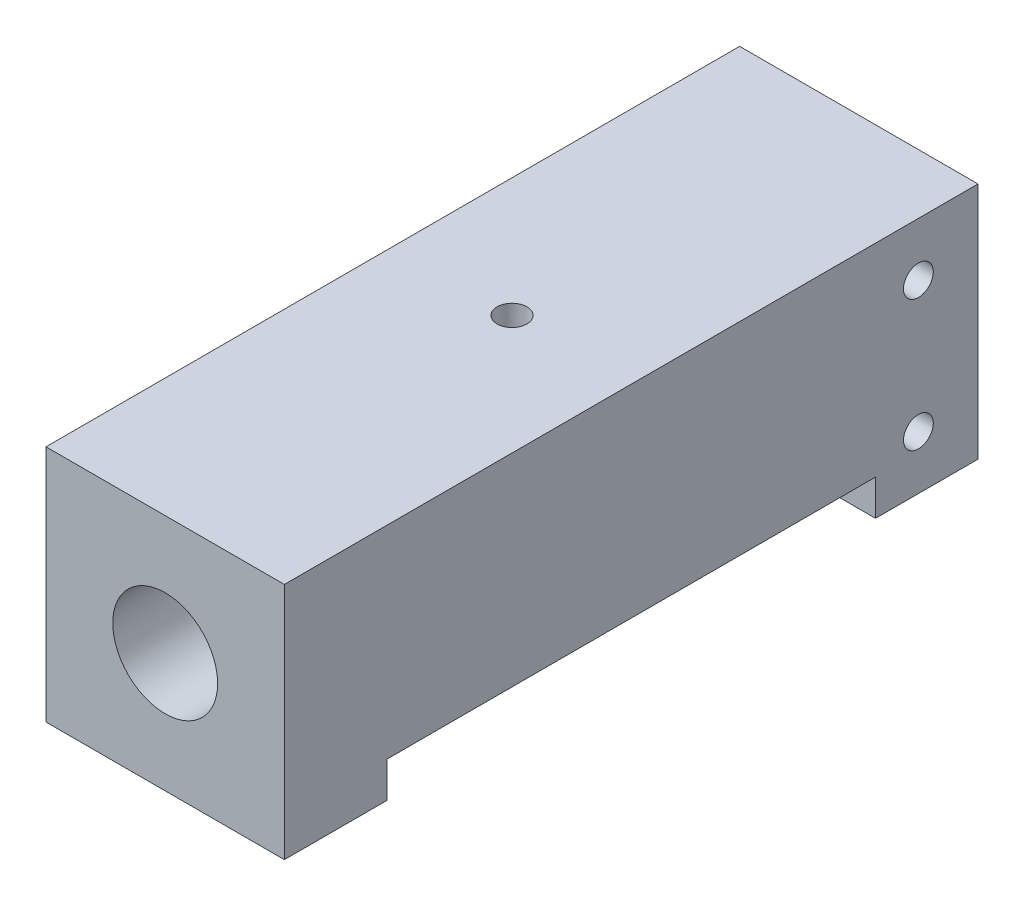
SolidWorks part; units mm, degrees
material "6063-T5"
ref_plane "Piano frontale" through (0, 0, 0) normal (0, 0, 1) x (1, 0, 0)
ref_plane "Piano superiore" through (0, 0, 0) normal (0, 1, 0) x (1, 0, 0)
ref_plane "Piano destro" through (0, 0, 0) normal (1, 0, 0) x (0, 0, -1)
sketch "Schizzo1" plane through (0, 0, 0) normal (0, 0, 1) x (1, 0, 0)
  line L1 (10, -10) -> (-10, -10)
  line L2 (10, -10) -> (10, 10)
  line L3 (10, 10) -> (-10, 10)
  line L4 (-10, -10) -> (-10, 10)
  line L5 (10, -10) -> (-10, 10) construction
  line L6 (10, 10) -> (-10, -10) construction
  point P0 (0, 0)
  dimension "D1" = 20
  dimension "D2" = 20
extrude "Estrusione-Estrusione1" add sketch "Schizzo1" against normal blind 58.2
sketch "Schizzo2" plane through (0, 0, -58.2) normal (0, 0, -1) x (-1, 0, 0)
  circle A0 centre (0, 0) radius 3
  dimension "D1" = 6
extrude "Taglio-Estrusione1" cut sketch "Schizzo2" against normal through all
sketch "Schizzo3" plane through (0, 0, -58.2) normal (0, 0, -1) x (-1, 0, 0)
  point P0 (0, 0)
hole_wizard "Foro filettato G1/8-1" positions "Schizzo8" profile "Schizzo7" tap size "G1/8" standard "BSI"
sketch "Schizzo8" plane through (0, 0, 0) normal (0, 0, 1) x (1, 0, 0)
  point P0 (0, 0)
sketch "Schizzo7" plane through (0, 0, 0) normal (1, 0, 0) x (0, -1, 0)
  line L0 (0, 0) -> (0, 12.6438)
  line L1 (0, 12.6438) -> (4.4, 10)
  line L2 (4.4, 10) -> (4.4, 0)
  line L5 (4.4, 0) -> (0, 0)
  line L10 (0, 12.6438) -> (-4.4, 10) construction
  line L11 (0, -6.35) -> (0, 107.95) construction
  dimension "Tap Drill Dia." = 8.8
  dimension "Tap Drill Depth" = 10
  dimension "Drill Angle" = 118
sketch "Schizzo11" plane through (0, 10, 0) normal (0, 1, 0) x (1, 0, 0)
  line L0 (0, 58.2) -> (0, 0) construction
  line L1 (10, 58.2) -> (-10, 58.2) construction
  line L2 (10, 29.1) -> (-10, 29.1) construction
  line L3 (10, 58.2) -> (10, 0) construction
  point P10 (0, 29.1)
  point P11 (0, 29.1)
  point P12 (0, 29.1)
hole_wizard "M3 Tapped Hole2" positions "Schizzo3D1" profile "Schizzo12" tap size "M3" standard "DIN"
sketch3d "Schizzo3D1"
  point P0 (0, 10, -29.1)
sketch "Schizzo12" plane through (0, 10, -29.1) normal (1, 0, 0) x (0, 0, 1)
  line L0 (0, 0) -> (0, 5.7511)
  line L1 (0, 5.7511) -> (1.25, 5)
  line L2 (1.25, 5) -> (1.25, 0)
  line L5 (1.25, 0) -> (0, 0)
  line L10 (0, 5.7511) -> (-1.25, 5) construction
  line L11 (0, -6.35) -> (0, 107.95) construction
  dimension "Tap Drill Dia." = 2.5
  dimension "Tap Drill Depth" = 5
  dimension "Drill Angle" = 118
cosmetic thread "Hole Thread4" parameters "D1"=5, "D2"=3
hole_wizard "Foro Ø16.0 (16)-1" positions "Schizzo3D3" profile "Schizzo14" hole size "Ø16.0" standard "ISO"
sketch3d "Schizzo3D3"
  point P0 (0, 0, 0)
  point P3 (0, 0, -58.2)
sketch "Schizzo14" plane through (0, 0, -58.2) normal (1, 0, 0) x (0, 1, 0)
  line L0 (0, 0) -> (0, 16.8069)
  line L1 (0, 16.8069) -> (8, 12)
  line L2 (8, 12) -> (8, 0)
  line L5 (8, 0) -> (0, 0)
  line L10 (0, 16.8069) -> (-8, 12) construction
  line L11 (0, -6.35) -> (0, 107.95) construction
  dimension "Hole Dia." = 16
  dimension "Hole Depth" = 12
  dimension "Drill Angle" = 118
sketch "Schizzo15" plane through (10, 0, 0) normal (1, 0, 0) x (0, 0, -1)
  line L0 (46.2, 0) -> (58.2, 0) construction
  line L1 (46.2, 8) -> (46.2, -8) construction
  line L4 (58.2, -10) -> (58.2, 10) construction
  line L6 (58.2, -10) -> (0, -10) construction
  point P5 (53.2, -5.5)
  point P8 (53.2, 5.5)
  dimension "D1" = 5.5
  dimension "D2" = 7
  dimension "D3" = 5
  dimension "D4" = 4.5
hole_wizard "M3 Tapped Hole3" positions "Schizzo3D4" profile "Schizzo16" tap size "M3" standard "ISO" end condition through all
sketch3d "Schizzo3D4"
  point P0 (10, 5.5, -53.2)
  point P3 (10, -5.5, -53.2)
sketch "Schizzo16" plane through (10, 5.5, -53.2) normal (0, 1, 0) x (0, 0, -1)
  line L0 (0, 0) -> (0, 20)
  line L1 (0, 20) -> (1.25, 20)
  line L2 (1.25, 20) -> (1.25, 0)
  line L5 (1.25, 0) -> (0, 0)
  line L11 (0, -6.35) -> (0, 107.95) construction
  dimension "Thread Major Dia." = 2.5
  dimension "Thru Tap Drill Depth" = 20
sketch "Sketch1" plane through (-10, 0, 0) normal (-1, 0, 0) x (0, 0, 1)
  line L0 (-58.2, 10) -> (-58.2, -10) construction
  line L1 (-58.2, 3) -> (-22, 3)
  line L2 (-58.2, 3) -> (-58.2, -3)
  line L3 (-58.2, -3) -> (-22, -3)
  line L4 (-22, 3) -> (-22, -3)
  line L5 (0, 10) -> (0, -10) construction
  line L6 (0, 0) -> (-22, 0) construction
  point P8 (-22, 0)
  dimension "D1" = 6
  dimension "D2" = 22
extrude "Boss-Extrude1" add sketch "Sketch1" along normal blind 4.9
sketch "Sketch2" plane through (10, 0, 0) normal (1, 0, 0) x (0, 0, -1)
  line L0 (58.2, -10) -> (0, -10) construction
  line L1 (49.6, -10) -> (33.6, -10)
  line L2 (49.6, -10) -> (49.6, -7)
  line L3 (49.6, -7) -> (33.6, -7)
  line L4 (33.6, -7) -> (8.6, -7)
  line L5 (41.6, -7) -> (41.6, -13) construction
  line L6 (8.6, -7) -> (8.6, -10)
  line L7 (8.6, -10) -> (33.6, -10)
  line L8 (0, -10) -> (8.6, -10) construction
  line L9 (49.6, -10) -> (58.2, -10) construction
  circle A2 centre (41.6, -13) radius 4 construction
  dimension "D1" = 16
  dimension "D2" = 3
extrude "Cut-Extrude1" cut sketch "Sketch2" against normal through all
